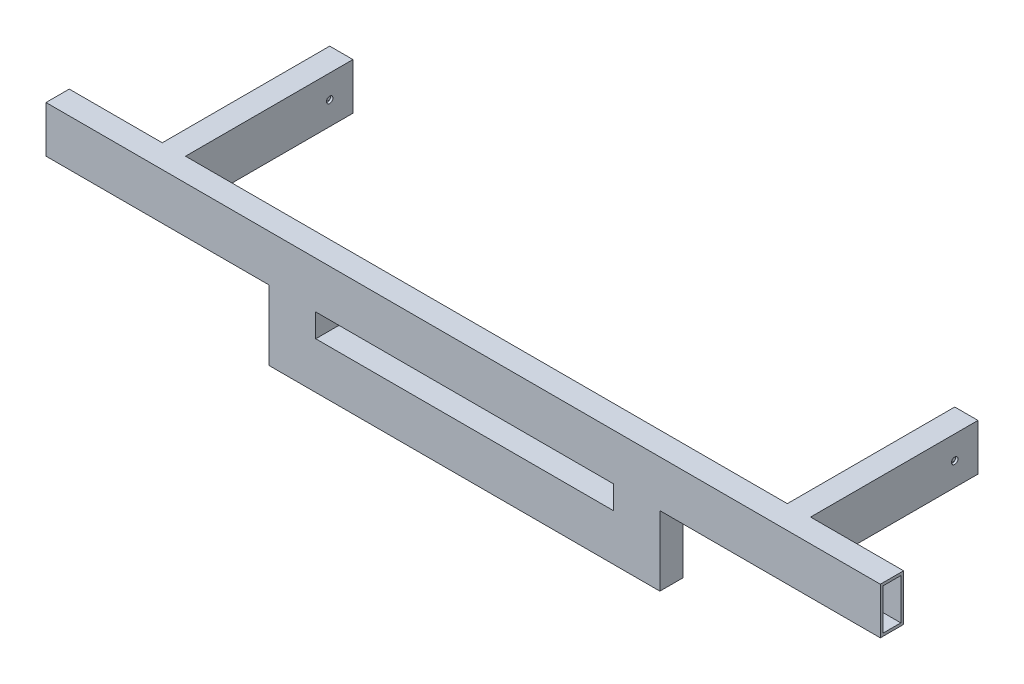
SolidWorks part; units mm, degrees
material "1060 Alloy"
ref_plane "Front Plane" through (0, 0, 0) normal (0, 0, 1) x (1, 0, 0)
ref_plane "Top Plane" through (0, 0, 0) normal (0, 1, 0) x (1, 0, 0)
ref_plane "Right Plane" through (0, 0, 0) normal (1, 0, 0) x (0, 0, -1)
sketch "Sketch1" plane through (0, 0, 0) normal (0, 0, 1) x (1, 0, 0)
  line L0 (351.9173, 12.6394) -> (588.9173, 12.6394)
  line L1 (-308.0827, 62.6394) -> (588.9173, 62.6394)
  line L2 (-308.0827, 62.6394) -> (-308.0827, 12.6394)
  line L3 (-308.0827, 12.6394) -> (-68.0827, 12.6394)
  line L4 (588.9173, 62.6394) -> (588.9173, 12.6394)
  line L6 (-68.0827, 12.6394) -> (-68.0827, -62.3606)
  line L7 (-68.0827, -62.3606) -> (351.9173, -62.3606)
  line L8 (351.9173, 12.6394) -> (351.9173, -62.3606)
  line L9 (-18.0827, 12.6394) -> (301.9173, 12.6394)
  line L10 (-18.0827, 12.6394) -> (-18.0827, -12.3606)
  line L11 (-18.0827, -12.3606) -> (301.9173, -12.3606)
  line L12 (301.9173, 12.6394) -> (301.9173, -12.3606)
  dimension "D1" = 897
  dimension "D2" = 50
  dimension "D3" = 50
  dimension "D4" = 75
  dimension "D5" = 50
  dimension "D6" = 50
  dimension "D7" = 420
  dimension "D8" = 240
extrude "Boss-Extrude1" add sketch "Sketch1" along normal blind 25
shell "Shell1" thickness 3 removed face at (-308.0827, 37.6394, 12.5) removed face at (588.9173, 37.6394, 12.5)
sketch "Sketch5" plane through (0, 0, 0) normal (0, 0, -1) x (-1, 0, 0)
  line L0 (18.0827, -12.3606) -> (-301.9173, -12.3606) construction
  line L1 (-231.9173, -12.3606) -> (-228.9173, -12.3606)
  line L2 (-231.9173, -12.3606) -> (-231.9173, -62.3606)
  line L3 (-231.9173, -62.3606) -> (-228.9173, -62.3606)
  line L4 (-228.9173, -12.3606) -> (-228.9173, -62.3606)
  line L5 (68.0827, -62.3606) -> (-351.9173, -62.3606) construction
  line L6 (-351.9173, -62.3606) -> (-351.9173, 12.6394) construction
  line L7 (-201.9173, -12.3606) -> (-201.9173, -62.3606)
  line L8 (-198.9173, -12.3606) -> (-198.9173, -62.3606)
  line L9 (-201.9173, -12.3606) -> (-198.9173, -12.3606)
  line L10 (-201.9173, -62.3606) -> (-198.9173, -62.3606)
  line L11 (-76.9173, -12.3606) -> (-76.9173, -62.3606)
  line L12 (-73.9173, -12.3606) -> (-73.9173, -62.3606)
  line L13 (-76.9173, -12.3606) -> (-73.9173, -12.3606)
  line L14 (-76.9173, -62.3606) -> (-73.9173, -62.3606)
  line L19 (-46.9173, -12.3606) -> (-46.9173, -62.3606)
  line L20 (-46.9173, -12.3606) -> (-43.9173, -12.3606)
  line L21 (-43.9173, -12.3606) -> (-43.9173, -62.3606)
  line L22 (-46.9173, -62.3606) -> (-43.9173, -62.3606)
  line L23 (-171.9173, -12.3606) -> (-171.9173, -62.3606) [skipped]
  line L24 (-168.9173, -12.3606) -> (-168.9173, -62.3606) [skipped]
  line L25 (-171.9173, -12.3606) -> (-168.9173, -12.3606) [skipped]
  line L26 (-171.9173, -62.3606) -> (-168.9173, -62.3606) [skipped]
  dimension "D1" = 3
  dimension "D2" = 120
  dimension "D3" = 2
  dimension "D4" = 2
  dimension "D5" = 2
extrude "Boss-Extrude3" add sketch "Sketch5" along normal blind 50
sketch "Sketch6" plane through (231.9173, 0, 0) normal (1, 0, 0) x (0, 0, -1)
  line L0 (50, -12.3606) -> (50, -62.3606) construction
  circle A0 centre (40, -35.4387) radius 3.5
  dimension "D2" = 7
  dimension "D1" = 10
extrude "Cut-Extrude1" cut sketch "Sketch6" against normal through all both and the other way through all
sketch "Sketch7" plane through (0, 0, 0) normal (0, 0, -1) x (-1, 0, 0)
  line L0 (-588.9173, 62.6394) -> (308.0827, 62.6394) construction
  line L1 (-488.9173, 62.6394) -> (-463.9173, 62.6394)
  line L2 (-488.9173, 62.6394) -> (-488.9173, 12.6394)
  line L3 (-488.9173, 12.6394) -> (-463.9173, 12.6394)
  line L4 (-463.9173, 62.6394) -> (-463.9173, 12.6394)
  line L5 (-351.9173, 12.6394) -> (-588.9173, 12.6394) construction
  line L6 (-588.9173, 12.6394) -> (-588.9173, 62.6394) construction
  line L7 (183.0827, 62.6394) -> (183.0827, 12.6394)
  line L8 (208.0827, 62.6394) -> (208.0827, 12.6394)
  line L9 (183.0827, 62.6394) -> (208.0827, 62.6394)
  line L10 (183.0827, 12.6394) -> (208.0827, 12.6394)
  line L11 (308.0827, 62.6394) -> (308.0827, 12.6394) construction
  point P10 (-588.9173, 37.6394)
  dimension "D1" = 25
  dimension "D2" = 100
  dimension "D4" = 100
  dimension "D3" = 2
extrude "Extrude-Thin1" add sketch "Sketch7" along normal blind 180 thin thin type one direction reverse wall 2.5
sketch "Sketch8" plane through (-208.0827, 0, 0) normal (-1, 0, 0) x (0, 0, 1)
  line L0 (-180, 12.6394) -> (-180, 62.6394) construction
  line L1 (-180, 12.6394) -> (0, 12.6394) construction
  circle A0 centre (-155, 37.6394) radius 3.5
  dimension "D2" = 25
  dimension "D3" = 7
  dimension "D1" = 25
extrude "Cut-Extrude2" cut sketch "Sketch8" against normal through all both and the other way through all
